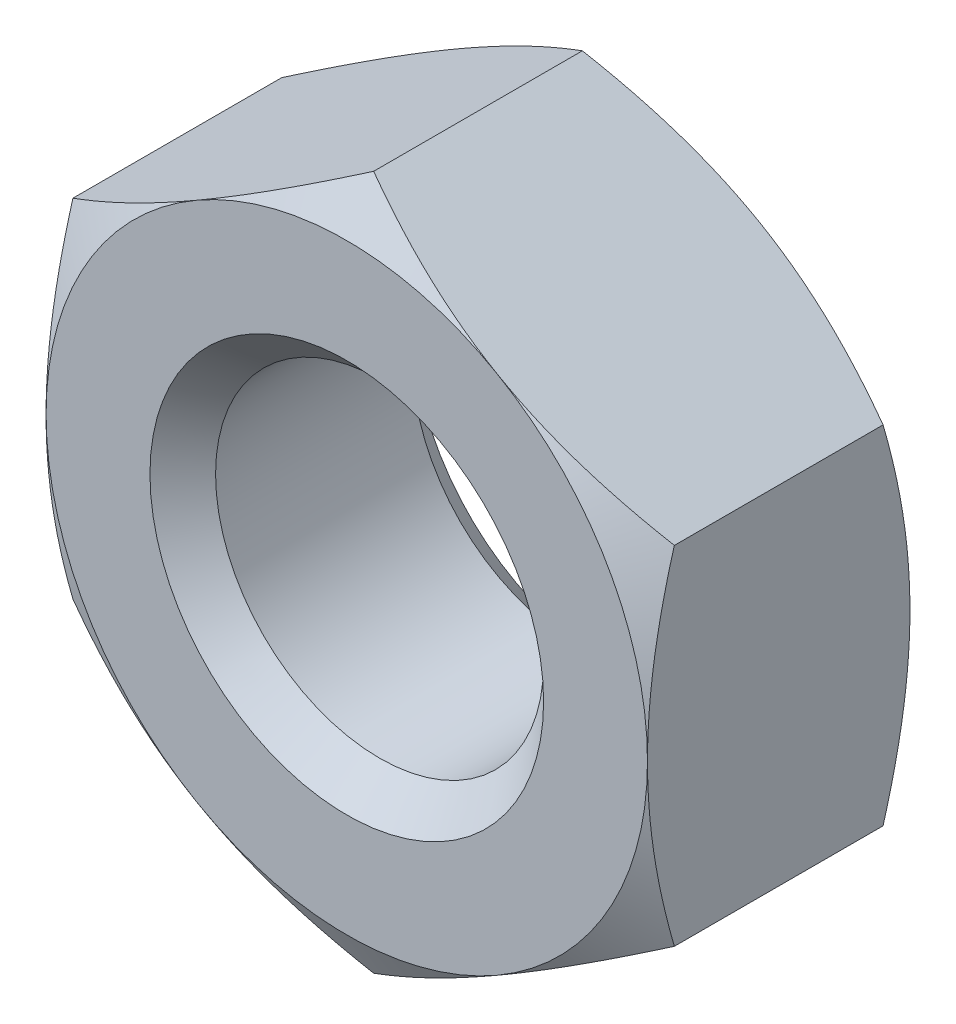
SolidWorks part; units mm, degrees
ref_plane "Front Plane" through (0, 0, 0) normal (0, 0, 1) x (1, 0, 0)
ref_plane "Top Plane" through (0, 0, 0) normal (0, 1, 0) x (1, 0, 0)
ref_plane "Right Plane" through (0, 0, 0) normal (1, 0, 0) x (0, 0, -1)
sketch "Sketch1" plane through (0, 0, 0) normal (0, 0, 1) x (1, 0, 0)
  line L1 (0, 3.1754) -> (-2.75, 1.5877)
  line L2 (-2.75, 1.5877) -> (-2.75, -1.5877)
  line L3 (-2.75, -1.5877) -> (0, -3.1754)
  line L4 (0, -3.1754) -> (2.75, -1.5877)
  line L5 (2.75, -1.5877) -> (2.75, 1.5877)
  line L6 (2.75, 1.5877) -> (0, 3.1754)
  circle A0 centre (0, 0) radius 2.75 construction
  circle A1 centre (0, 0) radius 1.5
  circle A3 centre (0, 0) radius 3.25
  dimension "D1" = 6.5
  dimension "D2" = 5.5
extrude "Boss-Extrude1" add sketch "Sketch1" along normal blind 2.4 contours A3 L6 L5 L4 L3 L2 L1 | L5 L6 L1 L2 L3 L4 A1 region at (1.333, 2.3088, 0) region at (-3.1581, 0, 0)
chamfer "Chamfer1" distance 0.5 angle 30 1 edges at (3.25, 0, 2.4) first distance on face at (3.25, 0, 2.4)
chamfer "Chamfer2" distance 0.5 angle 30 1 edges at (3.25, 0, 0) first distance on face at (3.25, 0, 0)
extrude "Cut-Extrude1" cut sketch "Sketch1<3>" along normal through all contours A3 L6 L5 L4 L3 L2 L1 region at (-3.1581, 0, 0)
sketch "Sketch1<3>" plane through (0, 0, 0) normal (0, 0, 1) x (1, 0, 0) same geometry as "Sketch1"
chamfer "Chamfer3" distance 0.3 angle 45 2 edges at (1.5, 0, 0) (1.5, 0, 2.4)
